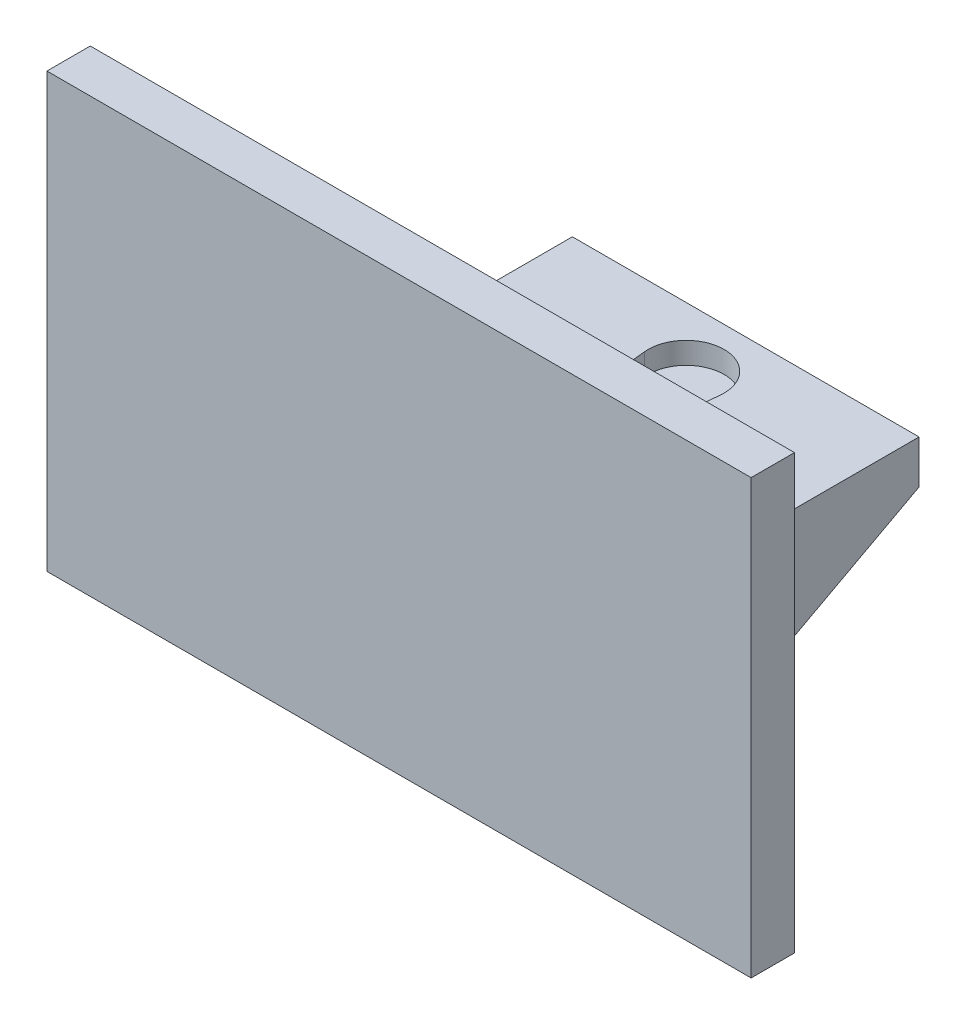
SolidWorks part; units mm, degrees
ref_plane "前视基准面" through (0, 0, 0) normal (0, 0, 1) x (1, 0, 0)
ref_plane "上视基准面" through (0, 0, 0) normal (0, 1, 0) x (1, 0, 0)
ref_plane "右视基准面" through (0, 0, 0) normal (1, 0, 0) x (0, 0, -1)
other "Configuration Table"
sketch "草图1" plane through (0, 0, 0) normal (0, 1, 0) x (1, 0, 0)
  line L0 (-3.4825, 10.15) -> (-1.99, -4.7)
  line L1 (-16, 16) -> (16, 16)
  line L2 (-16, 16) -> (-16, -16)
  line L3 (-16, -16) -> (16, -16)
  line L4 (16, 16) -> (16, -16)
  line L5 (-16, 16) -> (16, -16) construction
  line L6 (-16, -16) -> (16, 16) construction
  line L7 (-16, 16) -> (-12, 16)
  line L8 (-16, 16) -> (-16, -16)
  line L9 (-16, -16) -> (-12, -16)
  line L10 (-12, 16) -> (-12, -16)
  line L11 (-16, 16) -> (-12, -16) construction
  line L12 (-16, -16) -> (-12, 16) construction
  line L13 (16, 16) -> (12, 16)
  line L14 (16, 16) -> (16, -16)
  line L15 (16, -16) -> (12, -16)
  line L16 (12, 16) -> (12, -16)
  line L17 (16, 16) -> (12, -16) construction
  line L18 (16, -16) -> (12, 16) construction
  line L20 (-16, -16) -> (-16, -12.3128)
  line L23 (-32.5, -12) -> (32.5, -12)
  line L24 (-32.5, -12) -> (-32.5, -16)
  line L25 (-32.5, -16) -> (32.5, -16)
  line L26 (32.5, -12) -> (32.5, -16)
  line L27 (-32.5, -12) -> (32.5, -16) construction
  line L28 (-32.5, -16) -> (32.5, -12) construction
  line L29 (3.4825, 10.15) -> (1.99, -4.7)
  circle A0 centre (0, 10.5) radius 3.5
  circle A1 centre (0, -4.5) radius 2
  circle A2 centre (0, -2.5) radius 0.5
  point P0 (0, 0)
  point P14 (-14, 0)
  point P17 (14, 0)
  point P21 (9.9938, -14.5374)
  point P24 (0, -14)
  dimension "D1" = 7
  dimension "D2" = 4
  dimension "D3" = 1
  dimension "D6" = 5.5
  dimension "D4" = 15
  dimension "D5" = 13
  dimension "D7" = 32
  dimension "D8" = 32
  dimension "D9" = 4
  dimension "D10" = 65
  dimension "D11" = 4
  dimension "D12" = 4
extrude "凸台-拉伸2" add sketch "草图1" along normal blind 4 contours L10 L23 L16 L1 A2 A1 A0 region at (0, 0, -15.6312)
extrude "凸台-拉伸4" add sketch "草图1<5>" along normal blind 2 contours A2 A1 L29 A0 L0 | A0 | A2 A1 region at (0, 0, -2.7322) region at (0, 0, -10.5) region at (0, 0, 4.5542)
sketch "草图1<5>" plane through (0, 0, 0) normal (0, 1, 0) x (1, 0, 0) same geometry as "草图1"
extrude "凸台-拉伸5" add sketch "草图1<6>" along normal blind 25 and the other way blind 15 contours L2 L23 L10 L1 | L16 L23 L4 L1 | L23 L10 L3 L16 | L23 L8 L3 L10 | L24 L25 L8 L23 | L23 L16 L3 L14 | L26 L23 L14 L25 region at (-14, 0, -2) region at (-14, 0, 14) region at (-24.25, 0, 14) region at (14, 0, -2) region at (0, 0, 14) region at (14, 0, 14) region at (24.25, 0, 14)
sketch "草图1<6>" plane through (0, 0, 0) normal (0, 1, 0) x (1, 0, 0) same geometry as "草图1"
sketch "草图5" plane through (12, 0, 0) normal (-1, 0, 0) x (0, 0, 1)
  line L0 (-16, 4) -> (12, 25)
  line L1 (-16, 4) -> (-16, 25) construction
  line L2 (-16, 25) -> (12, 25) construction
  line L3 (12, 4) -> (12, 25) construction
  line L4 (12, 25) -> (-16, 25)
  line L5 (-16, 25) -> (-16, 4)
extrude "切除-拉伸1" cut sketch "草图5" against normal through all and the other way through all
sketch "草图6" plane through (12, 0, 0) normal (-1, 0, 0) x (0, 0, 1)
  line L0 (-16, 0) -> (12, -15)
  line L1 (-16, -15) -> (-16, 0) construction
  line L2 (12, -15) -> (-16, -15)
  line L3 (-16, -15) -> (-16, 0)
extrude "切除-拉伸2" cut sketch "草图6" against normal through all and the other way through all
sketch "草图8" plane through (12, 0, 0) normal (-1, 0, 0) x (0, 0, 1)
  line L0 (4.5, 4) -> (-16, 4)
  line L1 (-16, 4) -> (12, 4) construction
  line L2 (-16, 4) -> (12, 25) construction
  line L3 (-16, 4) -> (0.673, 16.5048)
  line L4 (0.673, 16.5048) -> (12, 25)
  line L5 (12, 25) -> (4.5, 4)
  dimension "D1" = 7.5
extrude "切除-拉伸4" cut sketch "草图8" against normal through all and the other way through all
